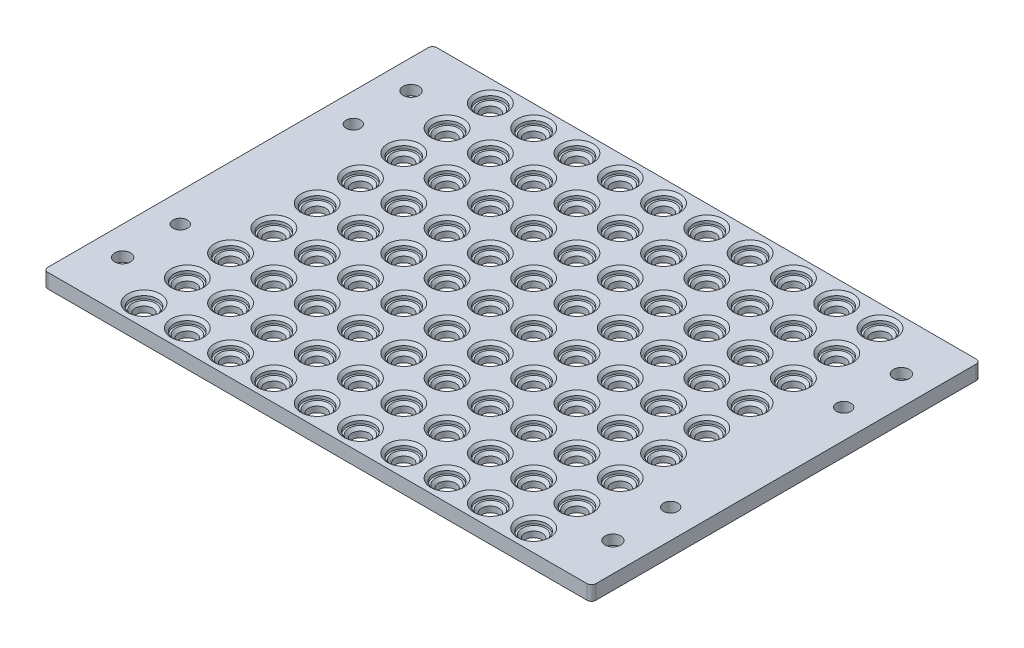
SolidWorks part; units mm, degrees
material "电木板A级"
ref_plane "前视" through (0, 0, 0) normal (0, 0, 1) x (1, 0, 0)
ref_plane "上视" through (0, 0, 0) normal (0, 1, 0) x (1, 0, 0)
ref_plane "右视" through (0, 0, 0) normal (1, 0, 0) x (0, 0, -1)
sketch "草图1" plane through (0, 0, 0) normal (0, 1, 0) x (1, 0, 0)
  line L1 (-190, -134.9) -> (190, -134.9)
  line L2 (-190, -134.9) -> (-190, 134.9)
  line L3 (-190, 134.9) -> (190, 134.9)
  line L4 (190, -134.9) -> (190, 134.9)
  line L5 (-190, -134.9) -> (190, 134.9) construction
  line L6 (-190, 134.9) -> (190, -134.9) construction
  point P0 (0, 0)
  dimension "D1" = 380
  dimension "D2" = 269.8
extrude "凸台-拉伸1" add sketch "草图1" along normal blind 10
hole_wizard "孔1" positions "草图3" profile "草图2" legacy end condition through all
sketch "草图3" plane through (0, 10, 0) normal (0, 1, 0) x (1, 0, 0)
  line L1 (0, 134.9) -> (0, 0) construction
  line L2 (190, 134.9) -> (-190, 134.9) construction
  line L3 (0, 0) -> (-190, 0) construction
  line L4 (-190, 134.9) -> (-190, -134.9) construction
  point P0 (-170, 60)
  point P17 (170, 60)
  point P18 (170, -60)
  point P19 (-170, -60)
  dimension "D1" = 340
  dimension "D2" = 120
sketch "草图2" plane through (-170, 10, -60) normal (1, 0, 0) x (0, 0, 1)
  line L0 (0, 0) -> (0, 10)
  line L1 (0, 10) -> (5, 10)
  line L2 (5, 10) -> (5, 0)
  line L3 (5, 0) -> (0, 0)
  line L4 (0, 110) -> (0, -10) construction
  dimension "直径" = 10
  dimension "深度" = 10
hole_wizard "孔3" positions "草图14" profile "草图13" legacy end condition through all
sketch "草图14" plane through (0, 10, 0) normal (0, 1, 0) x (1, 0, 0)
  line L0 (0, -134.9) -> (0, 0) construction
  line L1 (-190, -134.9) -> (190, -134.9) construction
  line L2 (0, 0) -> (190, 0) construction
  line L3 (190, -134.9) -> (190, 134.9) construction
  point P0 (135.099, -120.088)
  dimension "D1" = 270.198
  dimension "D2" = 240.176
sketch "草图13" plane through (135.099, 10, 120.088) normal (1, 0, 0) x (0, 0, 1)
  line L0 (0, 0) -> (0, 10)
  line L1 (0, 10) -> (6, 10)
  line L2 (6, 10) -> (6, 0)
  line L3 (6, 0) -> (0, 0)
  line L4 (0, 110) -> (0, -10) construction
  dimension "直径" = 12
  dimension "深度" = 10
hole_wizard "孔4" positions "草图16" profile "草图15" legacy
sketch "草图16" plane through (0, 10, 0) normal (0, 1, 0) x (1, 0, 0)
  point P0 (135.099, -120.088)
sketch "草图15" plane through (135.099, 10, 120.088) normal (1, 0, 0) x (0, 0, 1)
  line L0 (0, 0) -> (0, 4)
  line L1 (0, 4) -> (9.25, 4)
  line L2 (9.25, 4) -> (9.25, 0)
  line L3 (9.25, 0) -> (0, 0)
  line L4 (0, 110) -> (0, -10) construction
  dimension "直径" = 18.5
  dimension "深度" = 4
chamfer "倒角1" distance 2 angle 45 2 edges at (135.099, 6, 114.088) (135.099, 10, 129.338)
pattern_linear "阵列(线性)1" count 10 spacing 30.022 along (-1, 0, 0) count 9 spacing 30.022 along (0, 0, -1) of "孔3", "倒角1", "孔4"
hole_wizard "打孔尺寸根据内六角圆柱头螺钉的类型1" positions "草图12" profile "草图11" counterbore size "M6" standard "Gb" end condition through all
sketch "草图12" plane through (0, 10, 0) normal (0, 1, 0) x (1, 0, 0)
  line L0 (0, 134.9) -> (0, 0) construction
  line L2 (0, 0) -> (-190, 0) construction
  line L3 (-190, 134.9) -> (-190, -134.9) construction
  point P0 (-170, 100)
  point P15 (-170, -100)
  point P16 (170, -100)
  point P17 (170, 100)
  dimension "D1" = 200
sketch "草图11" plane through (-170, 10, -100) normal (1, 0, 0) x (0, 0, 1)
  line L0 (0, 0) -> (0, 10)
  line L1 (0, 10) -> (3.3, 10)
  line L3 (3.3, 10) -> (3.3, 6.8)
  line L4 (3.3, 6.8) -> (5.5, 6.8)
  line L5 (5.5, 6.8) -> (5.5, 0)
  line L7 (5.5, 0) -> (0, 0)
  line L11 (0, -6.35) -> (0, 107.95) construction
  dimension "通孔孔直径" = 6.6
  dimension "通孔孔深度" = 10
  dimension "柱形沉头孔直径" = 11
  dimension "柱形沉头孔深度" = 6.8
fillet "圆角1" radius 3 4 edges at (-190, 5, -134.9) (190, 5, -134.9) (190, 5, 134.9) (-190, 5, 134.9)
